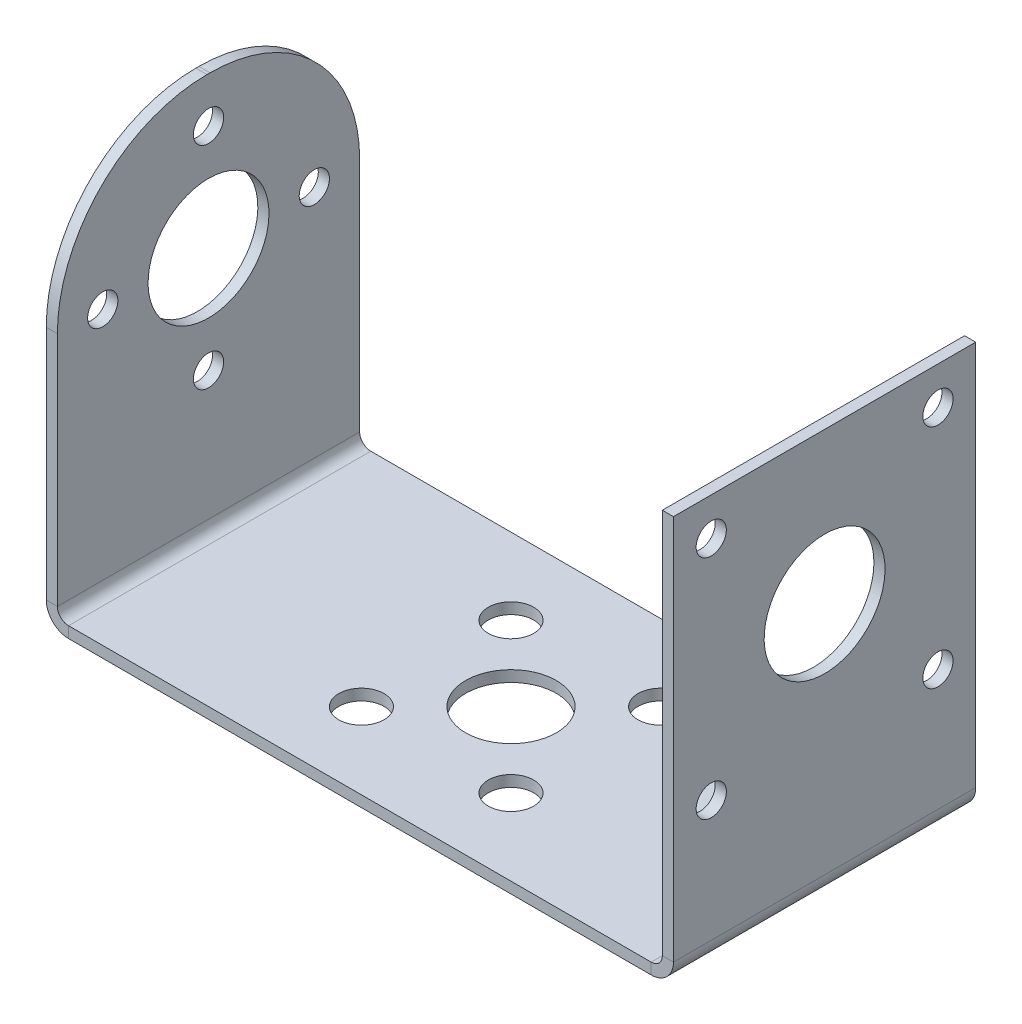
SolidWorks part; units mm, degrees
note: The reader was unsure of these and kept them because the rebuilt part matched: flange length of "边线-法兰1", "边线-法兰2".
ref_plane "前视基准面" through (0, 0, 0) normal (0, 0, 1) x (1, 0, 0)
ref_plane "上视基准面" through (0, 0, 0) normal (0, 1, 0) x (1, 0, 0)
ref_plane "右视基准面" through (0, 0, 0) normal (1, 0, 0) x (0, 0, -1)
other "Configuration Table"
sketch "草图1" plane through (0, 0, 0) normal (0, 1, 0) x (1, 0, 0)
  line L1 (-20.75, 10) -> (20.75, 10)
  line L2 (-20.75, 10) -> (-20.75, -10)
  line L3 (-20.75, -10) -> (20.75, -10)
  line L4 (20.75, 10) -> (20.75, -10)
  line L5 (-20.75, 10) -> (20.75, -10) construction
  line L6 (-20.75, -10) -> (20.75, 10) construction
  line L7 (-4.9495, 4.9495) -> (4.9495, 4.9495) construction
  line L8 (-4.9495, 4.9495) -> (-4.9495, -4.9495) construction
  line L9 (-4.9495, -4.9495) -> (4.9495, -4.9495) construction
  line L10 (4.9495, 4.9495) -> (4.9495, -4.9495) construction
  line L11 (-4.9495, 4.9495) -> (4.9495, -4.9495) construction
  line L12 (-4.9495, -4.9495) -> (4.9495, 4.9495) construction
  circle A0 centre (0, 0) radius 3
  circle A1 centre (4.9495, 4.9495) radius 1.5
  circle A2 centre (-4.9495, 4.9495) radius 1.5
  circle A3 centre (-4.9495, -4.9495) radius 1.5
  circle A4 centre (4.9495, -4.9495) radius 1.5
  point P0 (0, 0)
  dimension "D3" = 9.899
  dimension "D1" = 41.5
  dimension "D2" = 20
  dimension "D4" = 9.899
base flange "基体-法兰1" sketch "草图1" thickness 0.7366 reverse thickness direction no parameters "D1"=0.7366
edge flange "边线-法兰1" sketch "草图8" flange angle 90 flange length 27 flange position material inside bend radius 0.7366 thickness 0.7366 relief rectangular parameters "D6"=10
sketch "草图8" plane through (-20.75, 0, 0) normal (-1, 0, 0) x (0, 0, 1)
  line L0 (-10, -0.7366) -> (10, -0.7366) construction
  line L2 (-10, 0) -> (-10, 16.3634)
  line L3 (-0.1, 26.2634) -> (0.1, 26.2634)
  line L4 (10, 16.3634) -> (10, 0)
  line L11 (-10, 0) -> (10, 0) construction
  line L12 (-10, 0) -> (10, 0)
  circle A0 centre (0, 16.2634) radius 4
  circle A1 centre (0, 23.2634) radius 1
  circle A2 centre (-7, 16.2634) radius 1
  circle A3 centre (7, 16.2634) radius 1
  circle A4 centre (0, 9.2634) radius 1
  arc A5 (-10, 16.3634) -> (-0.1, 26.2634) centre (-0.1, 16.3634) cw
  arc A6 (0.1, 26.2634) -> (10, 16.3634) centre (0.1, 16.3634) cw
  point P16 (0, 0)
  point P21 (10, 26.2634)
  dimension "D2" = 17
  dimension "D4" = 7
  dimension "D8" = 9.9
  dimension "D9" = 9.9
  dimension "D10" = 2
  dimension "D11" = 2
  dimension "D12" = 2
  dimension "D13" = 2
  dimension "D14" = 8
  dimension "D1" = 26.2634
  dimension "D3" = 10
  dimension "D5" = 7
  dimension "D6" = 7
  dimension "D7" = 7
bend "边线折弯1" bend radius 0.7366 bend angle 90 parameters "D5"=1
edge flange "边线-法兰2" sketch "草图11" flange angle 90 flange length 27 flange position material inside bend radius 0.7366 thickness 0.7366 relief rectangular parameters "D6"=10
sketch "草图11" plane through (20.75, 0, 0) normal (1, 0, 0) x (0, 0, -1)
  line L0 (-10, 0) -> (10, 0) construction
  line L1 (-10, 0) -> (10, 0)
  line L2 (-10, 0) -> (-10, 26.2634)
  line L3 (-10, 26.2634) -> (10, 26.2634)
  line L4 (10, 26.2634) -> (10, 0)
bend "边线折弯2" bend radius 0.7366 bend angle 90 parameters "D5"=2
sketch "草图14" plane through (20.75, 0, 0) normal (1, 0, 0) x (0, 0, -1)
  line L0 (-10, 26.2634) -> (-10, 0.7366) construction
  line L1 (-7.5, 23.7634) -> (7.5, 23.7634) construction
  line L2 (-7.5, 23.7634) -> (-7.5, 8.7634) construction
  line L3 (-7.5, 8.7634) -> (7.5, 8.7634) construction
  line L4 (7.5, 23.7634) -> (7.5, 8.7634) construction
  line L5 (-7.5, 23.7634) -> (7.5, 8.7634) construction
  line L6 (-7.5, 8.7634) -> (7.5, 23.7634) construction
  line L8 (10, -0.7366) -> (-10, -0.7366) construction
  circle A0 centre (0, 16.2634) radius 4
  circle A1 centre (-7.5, 23.7634) radius 1
  circle A2 centre (7.5, 23.7634) radius 1
  circle A3 centre (7.5, 8.7634) radius 1
  circle A4 centre (-7.5, 8.7634) radius 1
  point P14 (-31.0436, 38.6896)
  dimension "D3" = 8
  dimension "D4" = 2
  dimension "D5" = 2
  dimension "D6" = 2
  dimension "D7" = 2
  dimension "D1" = 15
  dimension "D2" = 15
  dimension "D8" = 10
  dimension "D9" = 17
extrude "切除-拉伸1" cut sketch "草图14" against normal blind 10 normal cut yes
sketch "折弯-线1" plane through (0, 0, 0) normal (0, 1, 0) x (1, 0, 0)
sketch "边界框1" plane through (0, 0, 0) normal (0, 1, 0) x (1, 0, 0)
sheet metal parameters "钣金6" thickness 0.7366 parameters "D1"=0.7366
flat pattern "平板型式6" [suppressed]
sketch "折弯-线2" plane through (0, 0, 0) normal (0, 1, 0) x (1, 0, 0)
sketch "边界框2" [suppressed] plane through (0, 0, 0) normal (0, 1, 0) x (1, 0, 0)
sheet metal parameters "钣金7" thickness 0.7366 parameters "D1"=0.7366
flat pattern "平板型式6" [suppressed]
sketch "折弯-线2" plane through (0, 0, 0) normal (0, 1, 0) x (1, 0, 0)
sketch "边界框2" [suppressed] plane through (0, 0, 0) normal (0, 1, 0) x (1, 0, 0)
bend of the flat pattern "展平-<边线折弯1>1"
sheet metal parameters "钣金8" thickness 0.7366 parameters "D1"=0.7366
flat pattern "平板型式6" [suppressed]
sketch "折弯-线2" plane through (0, 0, 0) normal (0, 1, 0) x (1, 0, 0)
sketch "边界框2" [suppressed] plane through (0, 0, 0) normal (0, 1, 0) x (1, 0, 0)
bend of the flat pattern "展平-<边线折弯1>1"
bend of the flat pattern "展平-<边线折弯2>1"
sheet metal parameters "钣金9" thickness 0.7366 parameters "D1"=0.7366
flat pattern "平板型式6" [suppressed]
sketch "折弯-线2" plane through (0, 0, 0) normal (0, 1, 0) x (1, 0, 0)
sketch "边界框2" [suppressed] plane through (0, 0, 0) normal (0, 1, 0) x (1, 0, 0)
bend of the flat pattern "展平-<边线折弯1>1"
bend of the flat pattern "展平-<边线折弯2>1"
